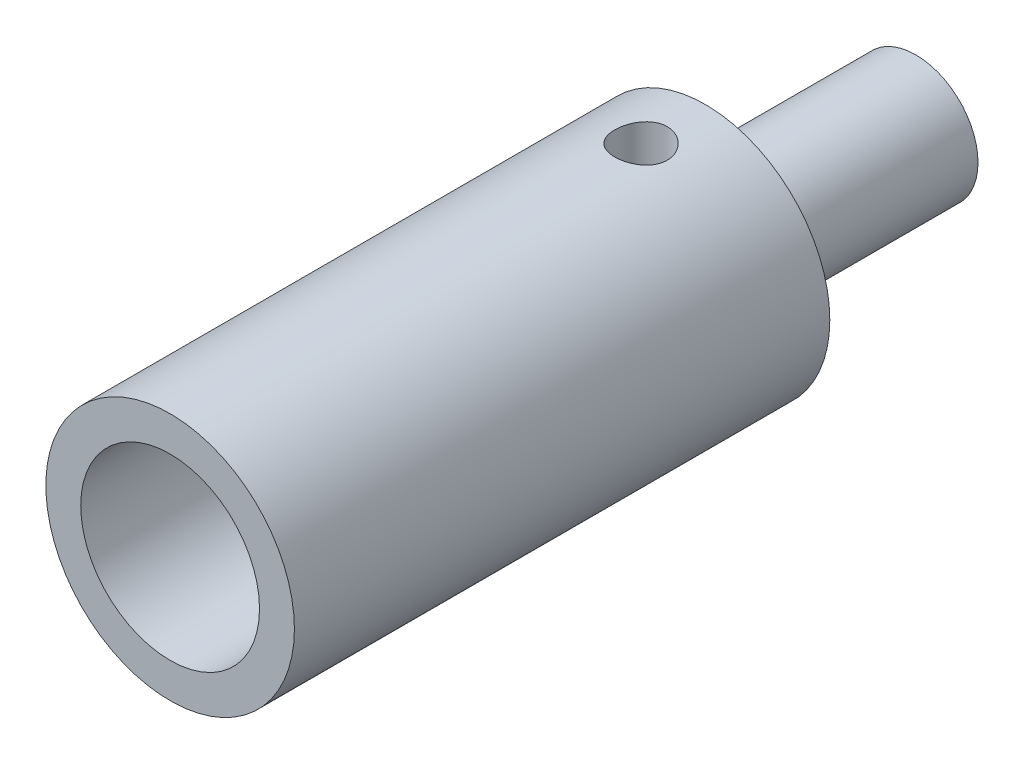
SolidWorks part; units mm, degrees
ref_plane "Alzado" through (0, 0, 0) normal (0, 0, 1) x (1, 0, 0)
ref_plane "Planta" through (0, 0, 0) normal (0, 1, 0) x (1, 0, 0)
ref_plane "Vista lateral" through (0, 0, 0) normal (1, 0, 0) x (0, 0, -1)
sketch "Croquis1" plane through (0, 0, 0) normal (0, 0, 1) x (1, 0, 0)
  circle A0 centre (0, 0) radius 13
  circle A1 centre (0, 0) radius 9.35
  dimension "D1" = 18.7
  dimension "D2" = 26
extrude "Saliente-Extruir1" add sketch "Croquis1" along normal blind 40
extrude "Saliente-Extruir2" add sketch "Croquis1<2>" against normal blind 16 contours A1 | A0 A1 region at (-12.6323, 0, 0) region at (0, 0, 0)
sketch "Croquis1<2>" plane through (0, 0, 0) normal (0, 0, 1) x (1, 0, 0) same geometry as "Croquis1"
sketch "Croquis2" plane through (0, 0, -16) normal (0, 0, -1) x (-1, 0, 0)
  circle A0 centre (0, 0) radius 6.5
  dimension "D1" = 13
extrude "Saliente-Extruir3" add sketch "Croquis2" along normal blind 22
fillet "Redondeo1" radius 0.5 1 edges at (-6.5, 0, -16)
fillet "Redondeo2" radius 0.5 1 edges at (9.35, 0, 0)
sketch "Croquis3" plane through (0, 0, 0) normal (0, 1, 0) x (1, 0, 0)
  line L1 (-24.5355, 12) -> (24.9531, 12) construction
  line L2 (13, 16) -> (-13, 16) construction
  circle A0 centre (0, 9.25) radius 2.75
  point P2 (24.9531, 8.3966)
  dimension "D1" = 5.5
  dimension "D2" = 4
extrude "Cortar-Extruir1" cut sketch "Croquis3" against normal through all both and the other way through all
